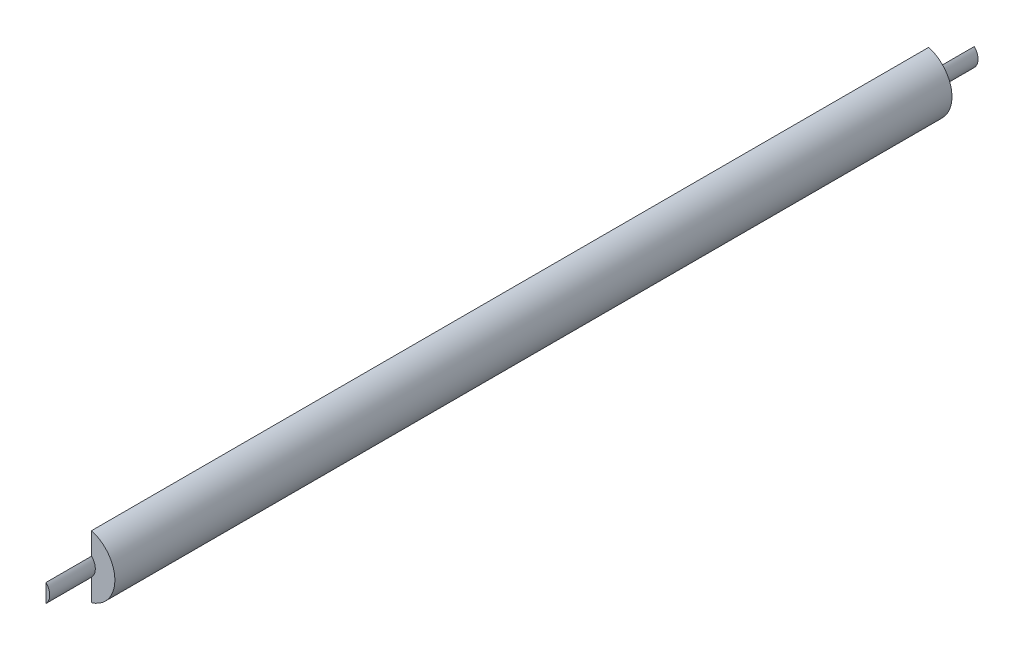
SolidWorks part; units mm, degrees
ref_plane "Ebene vorne" through (0, 0, 0) normal (0, 0, 1) x (1, 0, 0)
ref_plane "Ebene oben" through (0, 0, 0) normal (0, 1, 0) x (1, 0, 0)
ref_plane "Ebene rechts" through (0, 0, 0) normal (1, 0, 0) x (0, 0, -1)
sketch "Skizze1" plane through (0, 0, 0) normal (0, 0, 1) x (1, 0, 0)
  circle A0 centre (0, 0) radius 3.5
  dimension "D1" = 7
extrude "Aufsatz-Linear austragen1" add sketch "Skizze1" along normal blind 90
sketch "Skizze3" plane through (0, 0, 90) normal (0, 0, 1) x (1, 0, 0)
  circle A0 centre (0, 0) radius 1.4
  dimension "D1" = 2.8
sketch "Skizze4" plane through (0, 0, 0) normal (0, 0, -1) x (-1, 0, 0)
  circle A0 centre (0, 0) radius 1.4
  dimension "D1" = 2.8
extrude "Aufsatz-Linear austragen2" add sketch "Skizze3" along normal blind 4.9 contours A0
extrude "Aufsatz-Linear austragen3" add sketch "Skizze4" along normal blind 4.9
sketch "Skizze5" plane through (0, 0, 90) normal (0, 0, 1) x (1, 0, 0)
  line L0 (0, -3.5) -> (0, 3.5) construction
  line L2 (-1, 3.8684) -> (1, 3.8684)
  line L3 (-1, 3.8684) -> (-1, -4.1355)
  line L4 (-1, -4.1355) -> (1, -4.1355)
  line L5 (1, 3.8684) -> (1, -4.1355)
  circle A0 centre (0, 0) radius 3.5 construction
  dimension "D1" = 1
  dimension "D2" = 1
extrude "Schnitt-Linear austragen1" cut sketch "Skizze5" against normal through all and the other way through all
sketch "Skizze7" plane through (0, 0, 90) normal (0, 0, 1) x (1, 0, 0)
  line L1 (-4.5074, 3.9102) -> (-0.7895, 3.9102)
  line L2 (-4.5074, 3.9102) -> (-4.5074, -4.0064)
  line L3 (-4.5074, -4.0064) -> (-0.7895, -4.0064)
  line L4 (-0.7895, 3.9102) -> (-0.7895, -4.0064)
extrude "Schnitt-Linear austragen3" cut sketch "Skizze7" against normal through all and the other way blind 4.9
